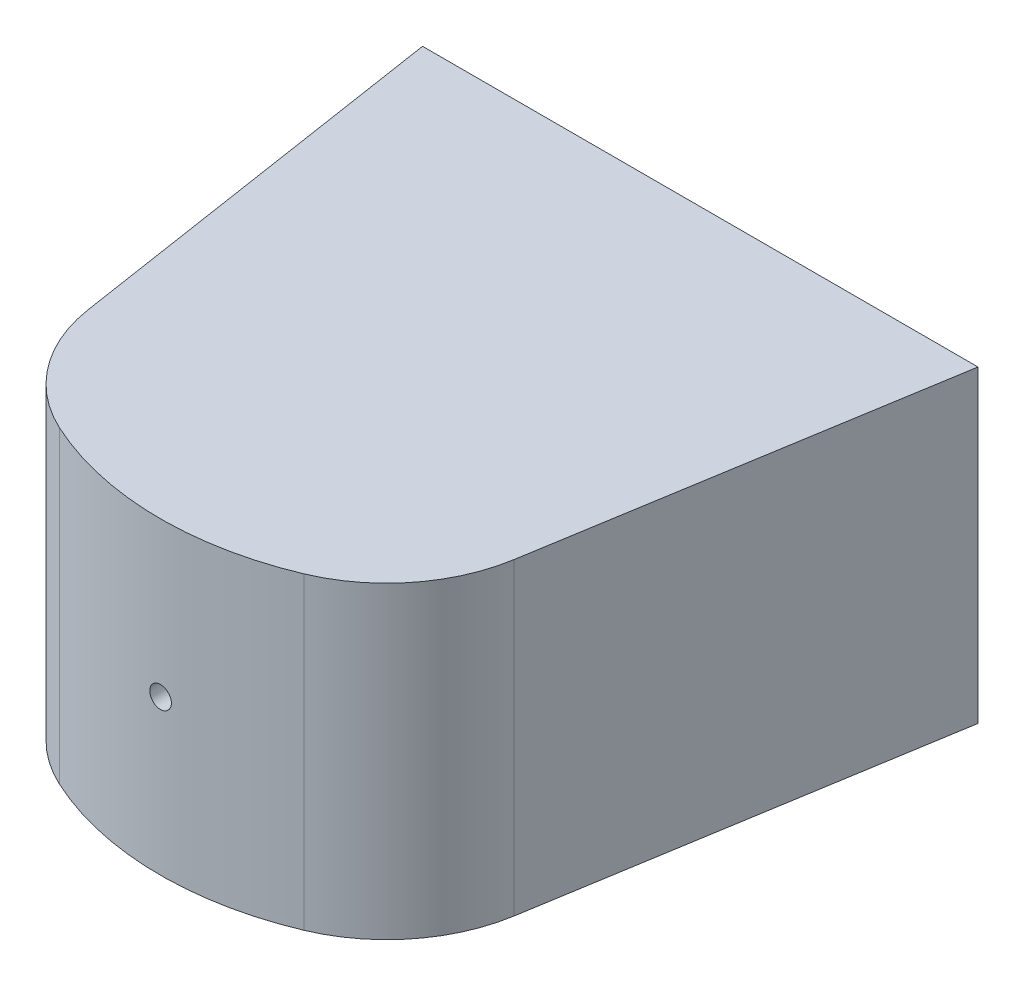
SolidWorks part; units mm, degrees
ref_plane "Front Plane" through (0, 0, 0) normal (0, 0, 1) x (1, 0, 0)
ref_plane "Top Plane" through (0, 0, 0) normal (0, 1, 0) x (1, 0, 0)
ref_plane "Right Plane" through (0, 0, 0) normal (1, 0, 0) x (0, 0, -1)
sketch "Sketch1" plane through (0, 0, 0) normal (0, 0, 1) x (1, 0, 0)
  line L1 (-20, 10) -> (20, 10)
  line L2 (-20, 10) -> (-20, -10)
  line L3 (-20, -10) -> (20, -10)
  line L4 (20, 10) -> (20, -10)
  line L5 (-20, 10) -> (20, -10) construction
  line L6 (-20, -10) -> (20, 10) construction
  point P0 (0, 0)
  dimension "D1" = 20
  dimension "D2" = 40
extrude "Boss-Extrude1" add sketch "Sketch1" along normal blind 35
fillet "Fillet1" 2 edges at (20, 0, 35) (-20, 0, 35) type full round first side face at (20, 0, 17.5) second side face at (-20, 0, 17.5) middle face at (0, 0, 35)
sketch "Sketch3" plane through (0, 0, 0) normal (0, 1, 0) x (1, 0, 0)
  line L0 (-12.6246, -34.9874) -> (-18.7203, 4.5747)
  line L1 (-12.6246, -34.9874) -> (-24.8759, -41.4791)
  line L2 (-18.7203, 4.5747) -> (-30.9716, -1.917)
  line L3 (-24.8759, -41.4791) -> (-30.9716, -1.917)
  line L4 (0, 0) -> (0, -42.8898) construction
  line L5 (18.7203, 4.5747) -> (30.9716, -1.917)
  line L6 (24.8759, -41.4791) -> (30.9716, -1.917)
  line L7 (12.6246, -34.9874) -> (24.8759, -41.4791)
  line L8 (12.6246, -34.9874) -> (18.7203, 4.5747)
extrude "Cut-Extrude1" cut sketch "Sketch3" against normal through all both and the other way through all contours L0 L2 L3 L1
sketch "Sketch4" plane through (0, 0, 0) normal (0, 1, 0) x (1, 0, 0)
  line L0 (11.9569, -36.7725) -> (19.2105, 7.5922)
  line L1 (11.9569, -36.7725) -> (26.7171, -51.3639)
  line L2 (19.2105, 7.5922) -> (33.9706, -6.9992)
  line L3 (26.7171, -51.3639) -> (33.9706, -6.9992)
extrude "Cut-Extrude2" cut sketch "Sketch4" against normal through all both and the other way through all
fillet "Fillet2" radius 10 1 edges at (13.0369, 0, 30.167)
fillet "Fillet3" radius 10 1 edges at (-13.4193, 0, 29.8298)
ref_plane "Plane1" through (0, 0, 33) normal (0, 0, 1) x (1, 0, 0)
sketch "Sketch7" plane through (0, 0, 33) normal (0, 0, 1) x (1, 0, 0)
  circle A0 centre (0, 0) radius 0.7
  dimension "D1" = 1.4
extrude "Cut-Extrude3" cut sketch "Sketch7" along normal blind 35
sketch "Sketch10" plane through (0, 0, 0) normal (0, 0, 1) x (1, 0, 0)
  circle A0 centre (-5, 0) radius 0.5
  circle A1 centre (5, 0) radius 0.5
extrude "Cut-Extrude4" cut sketch "Sketch10" along normal blind 5
